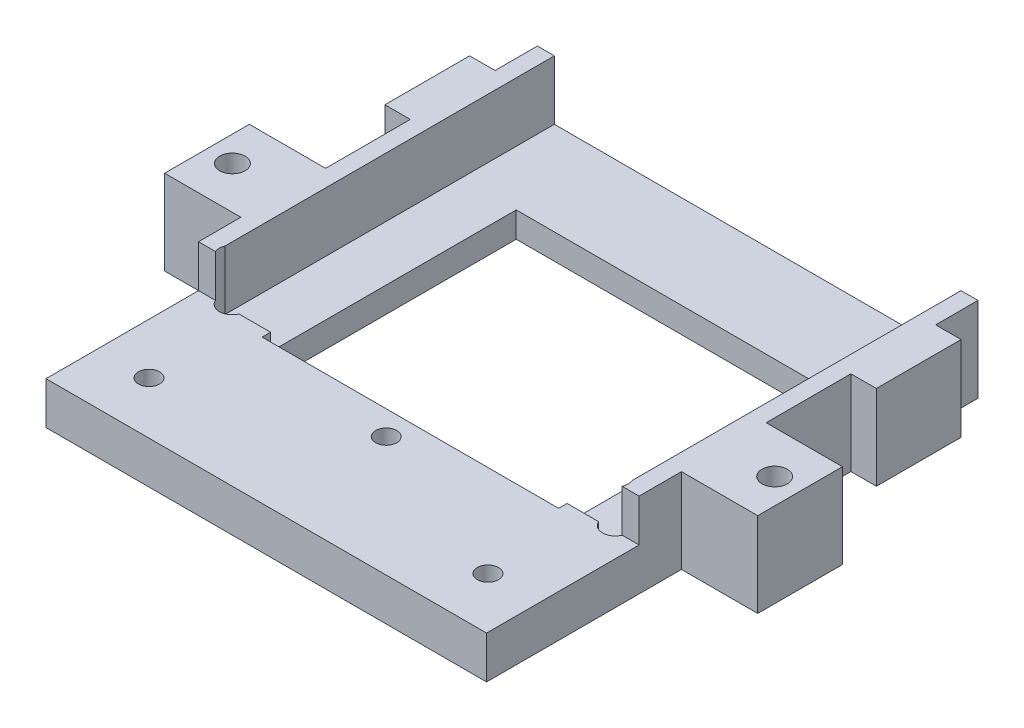
SolidWorks part; units mm, degrees
ref_plane "Front Plane" through (0, 0, 0) normal (0, 0, 1) x (1, 0, 0)
ref_plane "Top Plane" through (0, 0, 0) normal (0, 1, 0) x (1, 0, 0)
ref_plane "Right Plane" through (0, 0, 0) normal (1, 0, 0) x (0, 0, -1)
sketch "Sketch1" plane through (0, 0, 0) normal (0, 1, 0) x (1, 0, 0)
  line L1 (-26, -30) -> (26, -30)
  line L2 (-26, -30) -> (-26, 30)
  line L3 (-26, 30) -> (26, 30)
  line L4 (26, -30) -> (26, 30)
  line L5 (-26, -30) -> (26, 30) construction
  line L6 (-26, 30) -> (26, -30) construction
  point P0 (0, 0)
  dimension "D1" = 52
  dimension "D2" = 60
extrude "Boss-Extrude1" add sketch "Sketch1" along normal blind 10
sketch "Sketch2" plane through (0, 10, 0) normal (0, 1, 0) x (1, 0, 0)
  line L0 (26, -30) -> (26, 30) construction
  line L1 (-26, -30) -> (26, -30)
  line L2 (-26, -30) -> (-26, -10)
  line L3 (-26, -10) -> (-24, -10)
  line L4 (26, -30) -> (26, -10)
  line L5 (26, 30) -> (-26, 30) construction
  line L7 (-24, -10) -> (-24, 30)
  line L8 (-24, 30) -> (24, 30)
  line L9 (24, -10) -> (24, 30)
  line L10 (0, 0) -> (0, 30) construction
  line L11 (-26, 30) -> (-26, -30) construction
  line L12 (24, -10) -> (26, -10)
  dimension "D1" = 20
  dimension "D2" = 2
extrude "Cut-Extrude1" cut sketch "Sketch2" against normal blind 5
sketch "Sketch3" plane through (0, 5, 0) normal (0, 1, 0) x (1, 0, 0)
  line L0 (20, -21.8476) -> (-20, -21.8476) construction
  line L1 (0, 0) -> (0, -16.8476) construction
  circle A0 centre (-20, -21.8476) radius 1.25
  circle A1 centre (0, -13.8476) radius 1.25
  circle A2 centre (20, -21.8476) radius 1.25
  circle A3 centre (-20, -21.8476) radius 1.5 construction
  circle A4 centre (0, -13.8476) radius 1.2195 construction
  dimension "D1" = 2.5
  dimension "D4" = 40
extrude "Cut-Extrude2" cut sketch "Sketch3" against normal blind 5
sketch "Sketch5" plane through (0, 0, 0) normal (0, -1, 0) x (1, 0, 0)
  line L1 (-18.375, 24.6621) -> (-21.625, 24.6621)
  line L2 (-21.625, 24.6621) -> (-23.25, 21.8476)
  line L3 (-23.25, 21.8476) -> (-21.625, 19.033)
  line L4 (-21.625, 19.033) -> (-18.375, 19.033)
  line L5 (-18.375, 19.033) -> (-16.75, 21.8476)
  line L6 (-16.75, 21.8476) -> (-18.375, 24.6621)
  line L7 (1.625, 16.6621) -> (-1.625, 16.6621)
  line L8 (-1.625, 16.6621) -> (-3.25, 13.8476)
  line L9 (-3.25, 13.8476) -> (-1.625, 11.033)
  line L10 (-1.625, 11.033) -> (1.625, 11.033)
  line L11 (1.625, 11.033) -> (3.25, 13.8476)
  line L12 (3.25, 13.8476) -> (1.625, 16.6621)
  line L13 (21.625, 24.6621) -> (18.375, 24.6621)
  line L14 (18.375, 24.6621) -> (16.75, 21.8476)
  line L15 (16.75, 21.8476) -> (18.375, 19.033)
  line L16 (18.375, 19.033) -> (21.625, 19.033)
  line L17 (21.625, 19.033) -> (23.25, 21.8476)
  line L18 (23.25, 21.8476) -> (21.625, 24.6621)
  circle A2 centre (-20, 21.8476) radius 3.25
  circle A3 centre (-20, 21.8476) radius 3.25 construction
  circle A5 centre (0, 13.8476) radius 3.25
  circle A6 centre (0, 13.8476) radius 3.25 construction
  circle A7 centre (-20, 21.8476) radius 2.8146 construction
  circle A8 centre (20, 21.8476) radius 3.25
  circle A9 centre (20, 21.8476) radius 3.25 construction
  circle A10 centre (0, 13.8476) radius 2.8146 construction
  circle A11 centre (20, 21.8476) radius 2.8146 construction
  dimension "D1" = 2
  dimension "D2" = 2
  dimension "D3" = 2
extrude "Cut-Extrude3" cut sketch "Sketch5" against normal blind 3
sketch "Sketch6" plane through (0, 0, 0) normal (0, -1, 0) x (1, 0, 0)
  line L0 (-26, 30) -> (26, 30) construction
  line L1 (-17.5, -19) -> (17.5, -19)
  line L2 (-17.5, -19) -> (-17.5, 11)
  line L3 (-17.5, 11) -> (17.5, 11)
  line L4 (17.5, -19) -> (17.5, 11)
  line L5 (-17.5, -19) -> (17.5, 11) construction
  line L6 (-17.5, 11) -> (17.5, -19) construction
  line L7 (0, -4) -> (0, 0) construction
  point P0 (0, 0)
  dimension "D1" = 19
  dimension "D2" = 30
  dimension "D3" = 35
extrude "Cut-Extrude4" cut sketch "Sketch6" against normal through all
sketch "Sketch7" plane through (0, 10, 0) normal (0, 1, 0) x (1, 0, 0)
  line L1 (-26, 25) -> (-29, 25)
  line L2 (-26, 25) -> (-26, 15)
  line L3 (-26, 15) -> (-29, 15)
  line L4 (-29, 25) -> (-29, 15)
  line L5 (-24, 30) -> (-26, 30) construction
  dimension "D1" = 3
  dimension "D2" = 10
  dimension "D3" = 5
extrude "Boss-Extrude2" add sketch "Sketch7" against normal blind 10
pattern_linear "LPattern1" count 2 spacing 20 along (0, 0, 1) of "Boss-Extrude2"
mirror "Mirror1" about plane through (0, 0, 0) normal (1, 0, 0) of "LPattern1"
sketch "Sketch8" plane through (0, 5, 0) normal (0, 1, 0) x (1, 0, 0)
  line L1 (-24, 30) -> (24, 30)
  line L2 (-24, 30) -> (-24, -10)
  line L3 (-24, -10) -> (24, -10)
  line L4 (24, 30) -> (24, -10)
extrude "Cut-Extrude5" cut sketch "Sketch8" against normal blind 2
sketch "Sketch10" plane through (0, 10, 0) normal (0, 1, 0) x (1, 0, 0)
  line L0 (24, -10) -> (0, 0) construction
  line L1 (0, 0) -> (-24, -10) construction
  circle A0 centre (22.6154, -9.4231) radius 1.5
  circle A1 centre (-22.6154, -9.4231) radius 1.5
  dimension "D1" = 3
extrude "Cut-Extrude7" cut sketch "Sketch10" against normal blind 7
sketch "Sketch11" plane through (0, 0, 0) normal (0, -1, 0) x (1, 0, 0)
  line L0 (26, 30) -> (26, 5) construction
  line L1 (-26, 30) -> (26, 30)
  line L2 (-26, 30) -> (-26, 28)
  line L3 (-26, 28) -> (26, 28)
  line L4 (26, 30) -> (26, 28)
  dimension "D1" = 2
extrude "Cut-Extrude8" cut sketch "Sketch11" against normal blind 10
sketch "Sketch12" plane through (0, 0, 0) normal (0, -1, 0) x (1, 0, 0)
  line L0 (-35, -5) -> (-29, 5) construction
  line L1 (-29, 5) -> (-35, 5)
  line L2 (-29, 5) -> (-29, -5)
  line L3 (-29, -5) -> (-35, -5)
  line L4 (-35, 5) -> (-35, -5)
  line L5 (-26, -5) -> (-29, -5) construction
  circle A0 centre (-32, 0) radius 1.5
  dimension "D2" = 3
  dimension "D1" = 6
extrude "Boss-Extrude3" add sketch "Sketch12" against normal blind 10
mirror "Mirror2" about plane through (0, 0, 0) normal (1, 0, 0) of "Boss-Extrude3"
